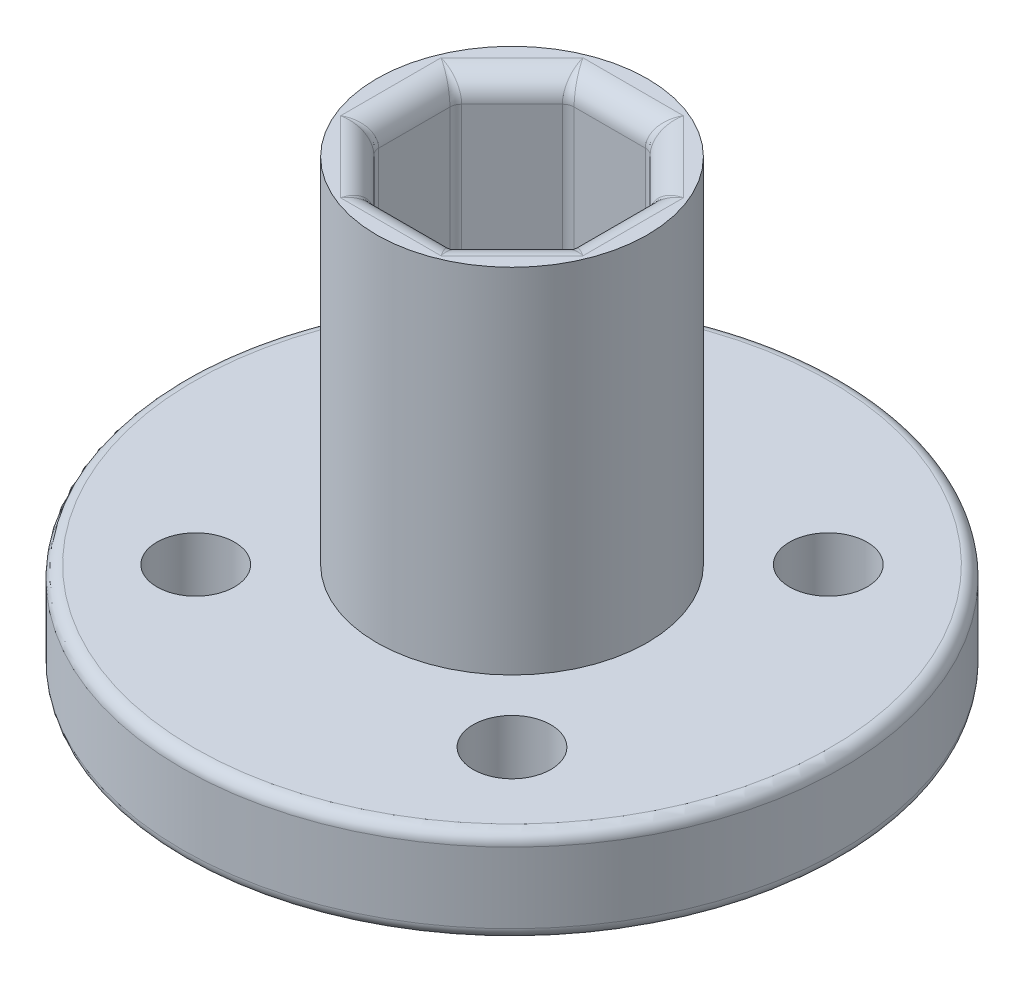
SolidWorks part; units mm, degrees
ref_plane "Front Plane" through (0, 0, 0) normal (0, 0, 1) x (1, 0, 0)
ref_plane "Top Plane" through (0, 0, 0) normal (0, 1, 0) x (1, 0, 0)
ref_plane "Right Plane" through (0, 0, 0) normal (1, 0, 0) x (0, 0, -1)
sketch "Sketch1" plane through (0, 0, 0) normal (0, 1, 0) x (1, 0, 0)
  circle A0 centre (0, 0) radius 14
  dimension "D1" = 28
extrude "Boss-Extrude1" add sketch "Sketch1" along normal blind 4 contours A0
sketch "Sketch3" plane through (0, 4, 0) normal (0, 1, 0) x (1, 0, 0)
  circle A0 centre (0, 0) radius 5.75
  dimension "D1" = 11.5
extrude "Boss-Extrude2" add sketch "Sketch3" along normal blind 15
sketch "Sketch6" plane through (0, 19, 0) normal (0, 1, 0) x (1, 0, 0)
  line L1 (1.719, 4.15) -> (-1.719, 4.15)
  line L2 (-1.719, 4.15) -> (-4.15, 1.719)
  line L3 (-4.15, 1.719) -> (-4.15, -1.719)
  line L4 (-4.15, -1.719) -> (-1.719, -4.15)
  line L5 (-1.719, -4.15) -> (1.719, -4.15)
  line L6 (1.719, -4.15) -> (4.15, -1.719)
  line L7 (4.15, -1.719) -> (4.15, 1.719)
  line L8 (4.15, 1.719) -> (1.719, 4.15)
  circle A0 centre (0, 0) radius 4.15 construction
  dimension "D1" = 8.3
extrude "Cut-Extrude3" cut sketch "Sketch6" against normal through all
sketch "Sketch5" plane through (0, 0, 0) normal (0, -1, 0) x (1, 0, 0)
  line L1 (-6.7175, -6.7175) -> (6.7175, -6.7175) construction
  line L2 (-6.7175, -6.7175) -> (-6.7175, 6.7175) construction
  line L3 (-6.7175, 6.7175) -> (6.7175, 6.7175) construction
  line L4 (6.7175, -6.7175) -> (6.7175, 6.7175) construction
  line L5 (-6.7175, -6.7175) -> (6.7175, 6.7175) construction
  line L6 (-6.7175, 6.7175) -> (6.7175, -6.7175) construction
  circle A0 centre (6.7175, 6.7175) radius 1.65
  circle A1 centre (-6.7175, 6.7175) radius 1.65
  circle A2 centre (-6.7175, -6.7175) radius 1.65
  circle A3 centre (6.7175, -6.7175) radius 1.65
  point P0 (0, 0)
  dimension "D2" = 3.3
  dimension "D1" = 9.5
extrude "Cut-Extrude2" cut sketch "Sketch5" against normal through all
chamfer "Chamfer1" distance 1.6 angle 45 4 edges at (6.7175, 0, -8.3675) (-6.7175, 0, -8.3675) (6.7175, 0, 5.0675) (-6.7175, 0, 5.0675)
fillet "Fillet1" radius 1 8 edges at (0, 19, 4.15) (-2.9345, 19, 2.9345) (-4.15, 19, 0) (-2.9345, 19, -2.9345) (0, 19, -4.15) (2.9345, 19, -2.9345) (4.15, 19, 0) (2.9345, 19, 2.9345)
fillet "Fillet2" radius 0.5 18 edges at (0, 0, 14) (0, 4, 14) (-1.719, 9, -4.15) (-4.15, 9, -1.719) (-4.15, 9, 1.719) (-1.719, 9, 4.15) (1.719, 9, 4.15) (4.15, 9, 1.719) (4.15, 9, -1.719) (1.719, 9, -4.15) (-1.8403, 18.7071, -4.4429) (-4.4429, 18.7071, -1.8403) (-4.4429, 18.7071, 1.8403) (-1.8403, 18.7071, 4.4429) (1.8403, 18.7071, 4.4429) (4.4429, 18.7071, 1.8403) (4.4429, 18.7071, -1.8403) (1.8403, 18.7071, -4.4429)
